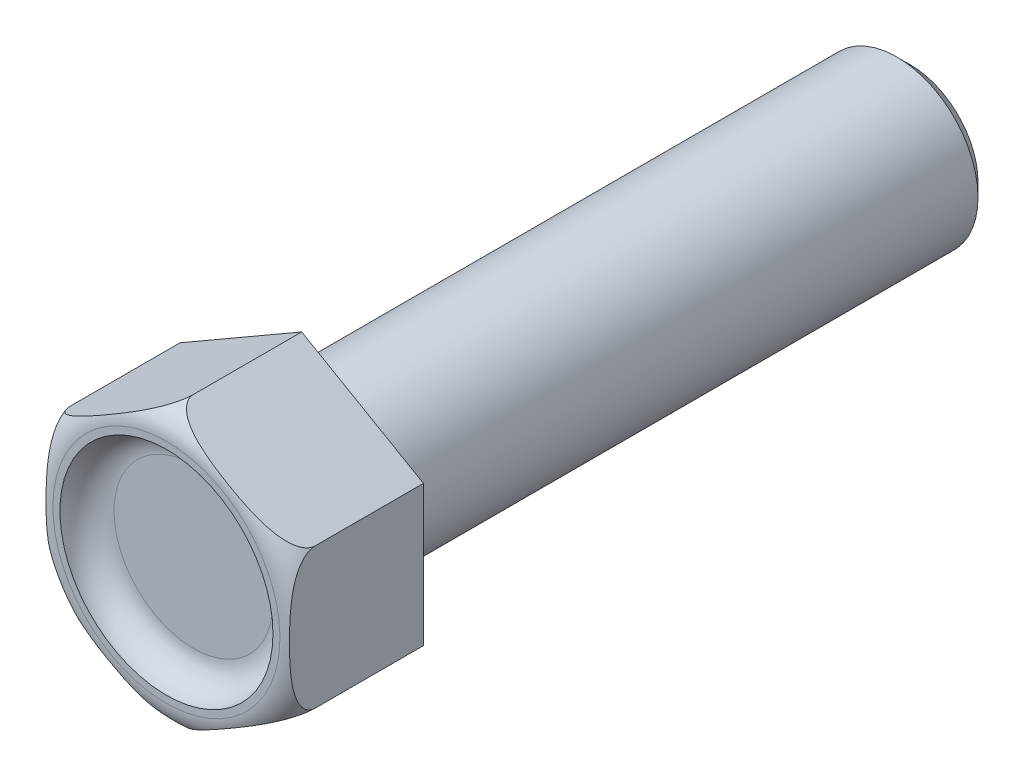
SolidWorks part; units mm, degrees
ref_plane "Front Plane" through (0, 0, 0) normal (0, 0, 1) x (1, 0, 0)
ref_plane "Top Plane" through (0, 0, 0) normal (0, 1, 0) x (1, 0, 0)
ref_plane "Right Plane" through (0, 0, 0) normal (1, 0, 0) x (0, 0, -1)
sketch "Sketch3" plane through (0, 0, 0) normal (0, 0, 1) x (1, 0, 0)
  line L1 (0, 10.3923) -> (-9, 5.1962)
  line L2 (-9, 5.1962) -> (-9, -5.1962)
  line L3 (-9, -5.1962) -> (0, -10.3923)
  line L4 (0, -10.3923) -> (9, -5.1962)
  line L5 (9, -5.1962) -> (9, 5.1962)
  line L6 (9, 5.1962) -> (0, 10.3923)
  circle A0 centre (0, 0) radius 9 construction
  dimension "D1" = 18
extrude "Boss-Extrude1" add sketch "Sketch3" along normal blind 10
sketch "Sketch4" plane through (0, 0, 0) normal (0, 0, -1) x (-1, 0, 0)
  circle A0 centre (0, 0) radius 6
  dimension "D1" = 12
extrude "Boss-Extrude2" add sketch "Sketch4" along normal blind 45
chamfer "Chamfer1" distance 1 angle 45 1 edges at (-6, 0, -45)
fillet "Fillet1" radius 0.5 1 edges at (-6, 0, 0)
sketch "Sketch5" plane through (0, 0, 0) normal (1, 0, 0) x (0, 0, -1)
  line L0 (-10, 5.1962) -> (-10, 10.3923) construction
  line L1 (-10, 10.3923) -> (0, 10.3923) construction
  line L2 (-8, 10.3923) -> (-10, 10.3923)
  line L3 (-10, 10.3923) -> (-10, 8.3923)
  line L4 (0, 0) -> (-10, 0) construction
  line L5 (-10, -5.1962) -> (-10, 5.1962) construction
  arc A0 (-10, 8.3923) -> (-8, 10.3923) centre (-8, 8.3923) cw
  dimension "D1" = 2
  dimension "D2" = 2
revolve "Cut-Revolve1" cut sketch "Sketch5" angle 360 about L4
sketch "Sketch6" plane through (0, 0, 10) normal (0, 0, 1) x (1, 0, 0)
  circle A0 centre (0, 0) radius 7.875
  dimension "D1" = 15.75
extrude "Cut-Extrude1" cut sketch "Sketch6" against normal blind 2
fillet "Fillet2" radius 2 1 edges at (7.875, 0, 8)
